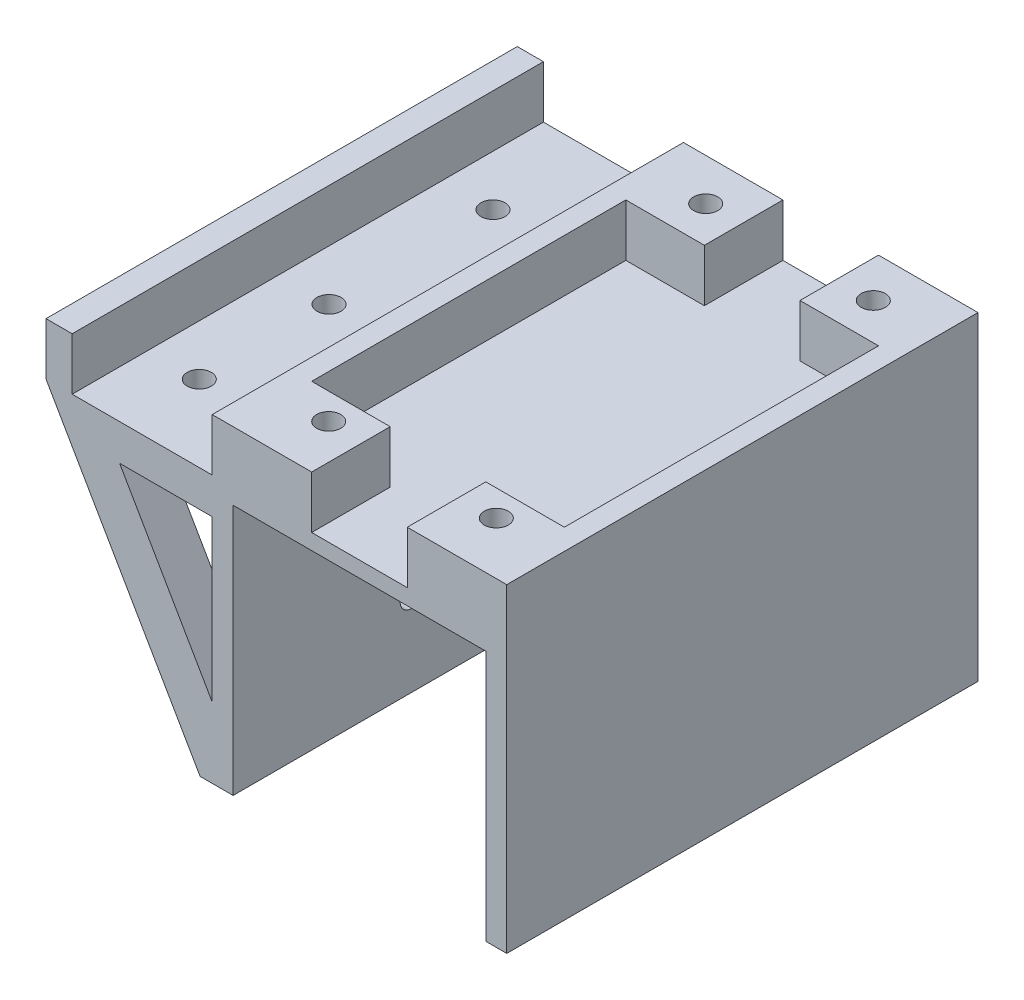
SolidWorks part; units mm, degrees
ref_plane "Front" through (0, 0, 0) normal (0, 0, 1) x (1, 0, 0)
ref_plane "Top" through (0, 0, 0) normal (0, 1, 0) x (1, 0, 0)
ref_plane "Right" through (0, 0, 0) normal (1, 0, 0) x (0, 0, -1)
sketch "Sketch1" plane through (0, 0, 0) normal (0, 0, 1) x (1, 0, 0)
  line L0 (0, 0) -> (0, 70)
  line L1 (0, 70) -> (56.254, 70)
  line L2 (56.254, 70) -> (56.254, 0)
  line L3 (56.254, 0) -> (52.254, 0)
  line L4 (52.254, 0) -> (52.254, 65)
  line L5 (52.254, 65) -> (4, 65)
  line L6 (4, 65) -> (4, 0)
  line L7 (4, 0) -> (0, 0)
  line L9 (4, 55) -> (52.254, 55)
  line L10 (4, 55) -> (4, 52)
  line L11 (4, 52) -> (52.254, 52)
  line L12 (52.254, 55) -> (52.254, 52)
  dimension "D1" = 48.254
  dimension "D2" = 4
  dimension "D3" = 4
  dimension "D4" = 5
  dimension "D5" = 70
  dimension "D6" = 3
  dimension "D7" = 10
extrude "Boss-Extrude1" add sketch "Sketch1" along normal blind 70 contours L7 L6 L5 L4 L3 L2 L1 L0 | L9 L12 L11 L10 region at (0.898, 35, 0)
sketch "Sketch3" plane through (0, 0, 70) normal (0, 0, 1) x (1, 0, 0)
  line L0 (0, 70) -> (-40.3946, 70)
  line L1 (-40.3946, 70) -> (0, 0.0344)
  line L2 (0, 0) -> (0, 70) construction
  line L3 (0, 0.0344) -> (0, 70)
  line L4 (0, 70) -> (0, 62.5)
  line L5 (0, 62.5) -> (-26, 62.5)
  line L6 (-26, 62.5) -> (0, 17.4667)
  line L7 (0, 17.4667) -> (0, 0.0344)
  line M11 (0, 70) -> (0, 0)
  dimension "D1" = 60
  dimension "D2" = 180
  dimension "D3" = 7.5
  dimension "D4" = 26
extrude "Boss-Extrude3" add sketch "Sketch3" against normal blind 8 contours L6 L5 L0 L1 M11 region at (-16.8587, 46.1047, 70)
sketch "Sketch4" plane through (0, 0, 0) normal (0, 0, -1) x (-1, 0, 0)
  line L0 (0, 70) -> (40.3946, 70)
  line L1 (40.3946, 70) -> (0, 0)
  line L2 (0, 0) -> (0, 17.4667)
  line L3 (0, 17.4667) -> (26, 62.5)
  line L4 (26, 62.5) -> (0, 62.5)
  line L5 (0, 62.5) -> (0, 70)
extrude "Boss-Extrude4" add sketch "Sketch4" against normal blind 8
ref_plane "Plane1" through (0, 0, 39) normal (0, 0, -1) x (-1, 0, 0)
sketch "Sketch5" plane through (0, 0, 39) normal (0, 0, -1) x (-1, 0, 0)
  line L0 (0, 62.5) -> (0, 70)
  line L1 (0, 70) -> (40.3946, 70)
  line L2 (40.3946, 70) -> (0, 0)
  line L3 (0, 0) -> (0, 17.4667)
  line L4 (0, 17.4667) -> (26, 62.5)
  line L5 (26, 62.5) -> (0, 62.5)
extrude "Boss-Extrude5" add sketch "Sketch5" along normal blind 8
sketch "Sketch6" plane through (0, 0, 0) normal (0, 0, -1) x (-1, 0, 0)
  line L5 (0, 62.5) -> (36.0666, 62.5)
  line L6 (0, 0) -> (40.3946, 70) construction
  line L7 (36.0666, 62.5) -> (40.3946, 70)
  line L8 (40.3946, 70) -> (0, 70)
  line L9 (40.3946, 70) -> (-56.254, 70) construction
  line L10 (0, 70) -> (0, 62.5)
  line L11 (-4, 0) -> (0, 0)
  line L12 (0, 0) -> (7.5019, 13)
  line L13 (7.5019, 13) -> (-4, 13)
  line L14 (-4, 52) -> (-4, 0) construction
  line L15 (-4, 13) -> (-4, 0)
  dimension "D1" = 13
extrude "Boss-Extrude6" add sketch "Sketch6" against normal blind 70
sketch "Sketch7" plane through (0, 0, 70) normal (0, 0, 1) x (1, 0, 0)
  line L0 (0, 17.4667) -> (0, 62.5) construction
  line L1 (-40.3946, 70) -> (0, 70)
  line L2 (-40.3946, 70) -> (-40.3946, 53)
  line L3 (-40.3946, 53) -> (0, 53)
  line L4 (0, 70) -> (0, 53)
  dimension "D1" = 17
extrude "Cut-Extrude3" cut sketch "Sketch7" against normal blind 70
sketch "Sketch8" plane through (0, 0, 0) normal (0, 0, -1) x (-1, 0, 0)
  line L1 (-4, 55) -> (-4, 52)
  line L2 (-4, 52) -> (-52.254, 52) construction
  line L3 (-4, 52) -> (30.0074, 52)
  line L4 (0, 0) -> (30.5845, 53) construction
  line L6 (30.0074, 52) -> (31.7386, 55)
  line L7 (31.7386, 55) -> (-4, 55)
  dimension "D1" = 180
extrude "Boss-Extrude7" add sketch "Sketch8" against normal blind 70
sketch "Sketch11" plane through (0, 0, 70) normal (0, 0, 1) x (1, 0, 0)
  line L0 (-31.7386, 55) -> (0, 0)
  line L3 (-31.7386, 55) -> (0, 55) construction
  line L4 (-27.289, 55) -> (-31.7386, 55)
  line L5 (-27.289, 55) -> (-3.0537, 13)
  line L6 (-3.0537, 13) -> (0, 0)
extrude "Boss-Extrude10" add sketch "Sketch11" against normal blind 8
sketch "Sketch12" plane through (0, 0, 70) normal (0, 0, 1) x (1, 0, 0)
  line L0 (-31.7386, 55) -> (-27.7598, 48.1051)
  line L1 (0, 0) -> (-31.7386, 55) construction
  line L2 (-27.7598, 48.1051) -> (0, 48.1051)
  line L3 (0, 17.4667) -> (0, 52) construction
  line L4 (0, 48.1051) -> (0, 55)
  line L5 (0, 55) -> (-31.7386, 55)
extrude "Boss-Extrude11" add sketch "Sketch12" against normal blind 70
sketch "Sketch13" plane through (0, 0, 0) normal (0, -1, 0) x (1, 0, 0)
  line L1 (67.4394, -10.6205) -> (-15.562, -10.6205)
  line L2 (67.4394, -10.6205) -> (67.4394, 77.2481)
  line L3 (67.4394, 77.2481) -> (-15.562, 77.2481)
  line L4 (-15.562, -10.6205) -> (-15.562, 77.2481)
extrude "Cut-Extrude4" cut sketch "Sketch13" against normal blind 4
sketch "Sketch14" plane through (0, 0, 70) normal (0, 0, 1) x (1, 0, 0)
  line L0 (-2.3083, 4) -> (-31.7386, 55)
  line L1 (-31.7386, 55) -> (0, 55)
  line L2 (0, 55) -> (0, 70)
  line L3 (0, 70) -> (56.254, 70)
  line L4 (56.254, 70) -> (56.254, 4)
  line L5 (56.254, 4) -> (52.254, 4)
  line L6 (52.254, 4) -> (52.254, 52)
  line L7 (52.254, 52) -> (4, 52)
  line L8 (4, 52) -> (4, 4)
  line L9 (4, 4) -> (-2.3083, 4)
  line L14 (-17.6891, 48.1051) -> (0, 48.1051)
  line L15 (52.254, 55) -> (4, 55)
  line L16 (52.254, 55) -> (52.254, 65)
  line L17 (52.254, 65) -> (4, 65)
  line L18 (4, 55) -> (4, 65)
  line L19 (-17.6891, 48.1051) -> (0, 48.1051) construction
  line L20 (0, 48.1051) -> (0, 17.4667)
  line L21 (0, 17.4667) -> (-17.6891, 48.1051)
extrude "Boss-Extrude12" add sketch "Sketch14" along normal blind 20
sketch "Sketch15" plane through (0, 0, 90) normal (0, 0, 1) x (1, 0, 0)
  line L0 (56.254, 4) -> (56.254, 70) construction
  line L1 (56.254, 65) -> (37.264, 65)
  line L2 (56.254, 65) -> (56.254, 55)
  line L3 (56.254, 55) -> (37.264, 55)
  line L4 (37.264, 65) -> (37.264, 55)
  line L5 (4, 55) -> (52.254, 55) construction
  dimension "D1" = 18.99
sketch "Sketch16" plane through (0, 0, 90) normal (0, 0, 1) x (1, 0, 0)
  line L1 (0, 70) -> (56.254, 70)
  line L2 (0, 70) -> (0, 65)
  line L3 (0, 65) -> (56.254, 65)
  line L4 (56.254, 70) -> (56.254, 65)
extrude "Cut-Extrude5" cut sketch "Sketch16" against normal blind 100
sketch "Sketch17" plane through (0, 65, 0) normal (0, 1, 0) x (1, 0, 0)
  line L1 (52.254, 0) -> (37.254, 0)
  line L2 (52.254, 0) -> (52.254, -15)
  line L3 (52.254, -15) -> (37.254, -15)
  line L4 (37.254, 0) -> (37.254, -15)
  line L5 (52.254, -90) -> (37.254, -90)
  line L6 (52.254, -90) -> (52.254, -75)
  line L7 (52.254, -75) -> (37.254, -75)
  line L8 (37.254, -90) -> (37.254, -75)
  dimension "D1" = 15
  dimension "D2" = 15
  dimension "D3" = 15
  dimension "D4" = 15
extrude "Boss-Extrude14" add sketch "Sketch17" against normal blind 13
sketch "Sketch21" plane through (0, 52, 0) normal (0, -1, 0) x (-1, 0, 0)
  circle A0 centre (-44.254, -80) radius 2.3
  circle A1 centre (-44.254, -8) radius 2.3
sketch "Sketch22" plane through (0, 52, 0) normal (0, -1, 0) x (1, 0, 0)
  line L1 (48.0965, 6.0036) -> (47.9041, 10.3295)
  line L2 (47.9041, 10.3295) -> (44.0617, 12.3259)
  line L3 (44.0617, 12.3259) -> (40.4115, 9.9964)
  line L4 (40.4115, 9.9964) -> (40.6039, 5.6705)
  line L5 (40.6039, 5.6705) -> (44.4463, 3.6741)
  line L6 (44.4463, 3.6741) -> (48.0965, 6.0036)
  line L7 (45.2007, 75.7746) -> (48.3866, 78.7072)
  line L8 (48.3866, 78.7072) -> (47.4399, 82.9325)
  line L9 (47.4399, 82.9325) -> (43.3073, 84.2254)
  line L10 (43.3073, 84.2254) -> (40.1214, 81.2928)
  line L11 (40.1214, 81.2928) -> (41.0681, 77.0675)
  line L12 (41.0681, 77.0675) -> (45.2007, 75.7746)
  circle A0 centre (44.254, 8) radius 3.75 construction
  circle A1 centre (44.254, 80) radius 3.75 construction
  point P10 (42.2366, 11.1611)
  dimension "D1" = 7.5
  dimension "D2" = 7.5
extrude "Cut-Extrude8" cut sketch "Sketch22" against normal blind 5
extrude "Cut-Extrude9" cut sketch "Sketch21" against normal blind 15
sketch "Sketch23" plane through (0, 0, 0) normal (-0.8661, -0.4998, 0) x (0, 0, 1)
  line L0 (90, 63.5007) -> (90, 4.6182) construction
  line L1 (70, 55.5401) -> (82, 55.5401)
  line L2 (70, 55.5401) -> (70, 15.0093)
  line L3 (70, 15.0093) -> (82, 15.0093)
  line L4 (82, 55.5401) -> (82, 15.0093)
  line L5 (62, 55.5401) -> (62, 15.0093) construction
  dimension "D1" = 8
  dimension "D2" = 8
extrude "Cut-Extrude10" cut sketch "Sketch23" against normal blind 9
sketch "Sketch25" plane through (0, 48.1051, 0) normal (0, -1, 0) x (-1, 0, 0)
  circle A0 centre (17.0755, -19.3006) radius 2.3
  circle A1 centre (17.0755, -50.6137) radius 2.3
extrude "Cut-Extrude11" cut sketch "Sketch25" against normal blind 20
sketch "Sketch26" plane through (0, 48.1051, 0) normal (0, -1, 0) x (1, 0, 0)
  circle A0 centre (-17.0755, 75.3913) radius 2.3
extrude "Cut-Extrude12" cut sketch "Sketch26" against normal blind 20
sketch "Sketch27" plane through (0, 0, 90) normal (0, 0, 1) x (1, 0, 0)
  line L0 (-23.3104, 48.1051) -> (-27.7598, 48.1051)
  line L1 (-31.7386, 55) -> (-2.3083, 4) construction
  line L2 (-27.7598, 48.1051) -> (-31.7386, 55)
  line L3 (-31.7386, 55) -> (-23.3104, 55)
  line L4 (0, 55) -> (-31.7386, 55) construction
  line L5 (-23.3104, 55) -> (-23.3104, 48.1051)
extrude "Boss-Extrude16" add sketch "Sketch27" against normal blind 20
sketch "Sketch28" plane through (0, 55, 0) normal (0, 1, 0) x (1, 0, 0)
  line L0 (4, -90) -> (37.254, -90) construction
  line L1 (4, 0) -> (19, 0)
  line L2 (4, 0) -> (4, -15)
  line L3 (4, -15) -> (19, -15)
  line L4 (19, 0) -> (19, -15)
  line L5 (4, -90) -> (19, -90)
  line L6 (4, -90) -> (4, -75)
  line L7 (4, -75) -> (19, -75)
  line L8 (19, -90) -> (19, -75)
  line L9 (4, 0) -> (4, -90) construction
  dimension "D1" = 15
  dimension "D2" = 15
  dimension "D3" = 15
  dimension "D4" = 15
extrude "Boss-Extrude17" add sketch "Sketch28" along normal blind 10
sketch "Sketch29" plane through (0, 52, 0) normal (0, -1, 0) x (-1, 0, 0)
  circle A0 centre (-12.254, -8) radius 2.3
  circle A1 centre (-12.254, -80) radius 2.3
extrude "Cut-Extrude13" cut sketch "Sketch29" against normal blind 20
sketch "Sketch30" plane through (0, 48.1051, 0) normal (0, -1, 0) x (1, 0, 0)
  line L1 (-27.7598, 70) -> (-17.3688, 70)
  line L2 (-27.7598, 70) -> (-27.7598, 82)
  line L3 (-27.7598, 82) -> (-17.3688, 82)
  line L4 (-17.3688, 70) -> (-17.3688, 82)
extrude "Boss-Extrude18" add sketch "Sketch30" against normal blind 5
sketch "Sketch31" plane through (0, 48.1051, 0) normal (0, -1, 0) x (1, 0, 0)
  circle A0 centre (-17.0755, 75.3913) radius 2.3
extrude "Cut-Extrude14" cut sketch "Sketch31" against normal blind 45
sketch "Sketch36" plane through (0, 55, 0) normal (0, 1, 0) x (1, 0, 0)
  line L0 (0, -90) -> (-31.7386, -90) construction
  line L1 (-31.7386, 0) -> (-31.1386, 0)
  line L2 (-31.7386, 0) -> (-31.7386, -90)
  line L3 (-31.7386, -90) -> (-31.1386, -90)
  line L4 (-31.1386, 0) -> (-31.1386, -90)
  line L5 (-27.5386, 0) -> (-27.5386, -90)
  line L6 (-27.5386, 0) -> (-26.9386, 0)
  line L7 (-26.9386, 0) -> (-26.9386, -90)
  line L8 (-27.5386, -90) -> (-26.9386, -90)
  line L9 (-23.3386, 0) -> (-23.3386, -90)
  line L10 (-23.3386, 0) -> (-22.7386, 0)
  line L11 (-22.7386, 0) -> (-22.7386, -90)
  line L12 (-23.3386, -90) -> (-22.7386, -90)
  line L13 (-19.1386, 0) -> (-19.1386, -90)
  line L14 (-19.1386, 0) -> (-18.5386, 0)
  line L15 (-18.5386, 0) -> (-18.5386, -90)
  line L16 (-19.1386, -90) -> (-18.5386, -90)
  line L17 (-14.9386, 0) -> (-14.9386, -90)
  line L18 (-14.9386, 0) -> (-14.3386, 0)
  line L19 (-14.3386, 0) -> (-14.3386, -90)
  line L20 (-14.9386, -90) -> (-14.3386, -90)
  line L21 (-10.7386, 0) -> (-10.7386, -90)
  line L22 (-10.7386, 0) -> (-10.1386, 0)
  line L23 (-10.1386, 0) -> (-10.1386, -90)
  line L24 (-10.7386, -90) -> (-10.1386, -90)
  line L25 (-6.5386, 0) -> (-6.5386, -90)
  line L26 (-6.5386, 0) -> (-5.9386, 0)
  line L27 (-5.9386, 0) -> (-5.9386, -90)
  line L28 (-6.5386, -90) -> (-5.9386, -90)
  line L29 (-2.3386, 0) -> (-2.3386, -90)
  line L30 (-2.3386, 0) -> (-1.7386, 0)
  line L31 (-1.7386, 0) -> (-1.7386, -90)
  line L32 (-2.3386, -90) -> (-1.7386, -90)
  line L33 (-31.7386, 0) -> (-27.5386, 0) construction
  dimension "D1" = 0.6
  dimension "D3" = 4.2
  dimension "D2" = 8
sketch "Sketch37" plane through (0, 55, 0) normal (0, 1, 0) x (1, 0, 0)
  line L0 (19, 0) -> (37.254, 0) construction
  line L13 (4, -6) -> (4, -6.5)
  line L14 (4, -15) -> (4, -75) construction
  line L15 (4, -2) -> (53, -2)
  line L16 (4, -2) -> (4, -2.5)
  line L17 (4, -2.5) -> (53, -2.5)
  line L18 (53, -2) -> (53, -2.5)
  line L19 (4, -6) -> (53, -6)
  line L20 (53, -6) -> (53, -6.5)
  line L21 (4, -6.5) -> (53, -6.5)
  line L22 (4, -10) -> (4, -10.5)
  line L23 (4, -10) -> (53, -10)
  line L24 (53, -10) -> (53, -10.5)
  line L25 (4, -10.5) -> (53, -10.5)
  line L26 (4, -14) -> (4, -14.5)
  line L27 (4, -14) -> (53, -14)
  line L28 (53, -14) -> (53, -14.5)
  line L29 (4, -14.5) -> (53, -14.5)
  line L30 (4, -18) -> (4, -18.5)
  line L31 (4, -18) -> (53, -18)
  line L32 (53, -18) -> (53, -18.5)
  line L33 (4, -18.5) -> (53, -18.5)
  line L34 (4, -22) -> (4, -22.5)
  line L35 (4, -22) -> (53, -22)
  line L36 (53, -22) -> (53, -22.5)
  line L37 (4, -22.5) -> (53, -22.5)
  line L38 (4, -26) -> (4, -26.5)
  line L39 (4, -26) -> (53, -26)
  line L40 (53, -26) -> (53, -26.5)
  line L41 (4, -26.5) -> (53, -26.5)
  line L42 (4, -30) -> (4, -30.5)
  line L43 (4, -30) -> (53, -30)
  line L44 (53, -30) -> (53, -30.5)
  line L45 (4, -30.5) -> (53, -30.5)
  line L46 (4, -34) -> (4, -34.5)
  line L47 (4, -34) -> (53, -34)
  line L48 (53, -34) -> (53, -34.5)
  line L49 (4, -34.5) -> (53, -34.5)
  line L50 (4, -38) -> (4, -38.5)
  line L51 (4, -38) -> (53, -38)
  line L52 (53, -38) -> (53, -38.5)
  line L53 (4, -38.5) -> (53, -38.5)
  line L54 (4, -42) -> (4, -42.5)
  line L55 (4, -42) -> (53, -42)
  line L56 (53, -42) -> (53, -42.5)
  line L57 (4, -42.5) -> (53, -42.5)
  line L58 (4, -46) -> (4, -46.5)
  line L59 (4, -46) -> (53, -46)
  line L60 (53, -46) -> (53, -46.5)
  line L61 (4, -46.5) -> (53, -46.5)
  line L62 (4, -50) -> (4, -50.5)
  line L63 (4, -50) -> (53, -50)
  line L64 (53, -50) -> (53, -50.5)
  line L65 (4, -50.5) -> (53, -50.5)
  line L66 (4, -54) -> (4, -54.5)
  line L67 (4, -54) -> (53, -54)
  line L68 (53, -54) -> (53, -54.5)
  line L69 (4, -54.5) -> (53, -54.5)
  line L70 (4, -58) -> (4, -58.5)
  line L71 (4, -58) -> (53, -58)
  line L72 (53, -58) -> (53, -58.5)
  line L73 (4, -58.5) -> (53, -58.5)
  line L74 (4, -62) -> (4, -62.5)
  line L75 (4, -62) -> (53, -62)
  line L76 (53, -62) -> (53, -62.5)
  line L77 (4, -62.5) -> (53, -62.5)
  line L78 (4, -66) -> (4, -66.5)
  line L79 (4, -66) -> (53, -66)
  line L80 (53, -66) -> (53, -66.5)
  line L81 (4, -66.5) -> (53, -66.5)
  line L82 (4, -70) -> (4, -70.5)
  line L83 (4, -70) -> (53, -70)
  line L84 (53, -70) -> (53, -70.5)
  line L85 (4, -70.5) -> (53, -70.5)
  line L86 (4, -74) -> (4, -74.5)
  line L87 (4, -74) -> (53, -74)
  line L88 (53, -74) -> (53, -74.5)
  line L89 (4, -74.5) -> (53, -74.5)
  line L90 (4, -78) -> (4, -78.5)
  line L91 (4, -78) -> (53, -78)
  line L92 (53, -78) -> (53, -78.5)
  line L93 (4, -78.5) -> (53, -78.5)
  line L94 (4, -82) -> (4, -82.5)
  line L95 (4, -82) -> (53, -82)
  line L96 (53, -82) -> (53, -82.5)
  line L97 (4, -82.5) -> (53, -82.5)
  line L98 (4, -86) -> (4, -86.5)
  line L99 (4, -86) -> (53, -86)
  line L100 (53, -86) -> (53, -86.5)
  line L101 (4, -86.5) -> (53, -86.5)
  dimension "D1" = 49
  dimension "D2" = 0.5
  dimension "D3" = 2
  dimension "D4" = 22
sketch "Sketch40" plane through (0, 65, 0) normal (0, 1, 0) x (1, 0, 0)
  circle A0 centre (-17.0755, -19.3006) radius 2.2732
  circle A1 centre (-17.0755, -50.6137) radius 2.3827
  circle A2 centre (-17.0755, -75.3913) radius 2.3828
  circle A3 centre (12.254, -80) radius 2.5607
  circle A4 centre (44.254, -80) radius 2.2791
  circle A5 centre (44.254, -8) radius 2.3112
  circle A6 centre (12.254, -8) radius 2.3
sketch "Sketch41" plane through (0, 55, 0) normal (0, 1, 0) x (1, 0, 0)
  line L0 (-31.7386, 0) -> (0, 0) construction
  line L1 (-31.7386, -90) -> (-26.7386, -90)
  line L2 (-31.7386, -90) -> (-31.7386, 0)
  line L3 (-31.7386, 0) -> (-26.7386, 0)
  line L4 (-26.7386, -90) -> (-26.7386, 0)
  dimension "D1" = 5
extrude "Boss-Extrude19" add sketch "Sketch41" along normal blind 10
sketch "Sketch42" plane through (0, 52, 0) normal (0, -1, 0) x (1, 0, 0)
  line L1 (14.1516, 76.1078) -> (16.5735, 79.6973)
  line L2 (16.5735, 79.6973) -> (14.6759, 83.5895)
  line L3 (14.6759, 83.5895) -> (10.3564, 83.8922)
  line L4 (10.3564, 83.8922) -> (7.9345, 80.3027)
  line L5 (7.9345, 80.3027) -> (9.8321, 76.4105)
  line L6 (9.8321, 76.4105) -> (14.1516, 76.1078)
  line L7 (13.8189, 3.9626) -> (16.533, 7.3365)
  line L8 (16.533, 7.3365) -> (14.9681, 11.374)
  line L9 (14.9681, 11.374) -> (10.6891, 12.0374)
  line L10 (10.6891, 12.0374) -> (7.975, 8.6635)
  line L11 (7.975, 8.6635) -> (9.5399, 4.626)
  line L12 (9.5399, 4.626) -> (13.8189, 3.9626)
  circle A0 centre (12.254, 80) radius 3.75 construction
  circle A1 centre (12.254, 8) radius 3.75 construction
  dimension "D1" = 7.5
  dimension "D2" = 7.5
extrude "Cut-Extrude15" cut sketch "Sketch42" against normal blind 5
sketch "Sketch43" plane through (4, 0, 0) normal (1, 0, 0) x (0, 0, -1)
  circle A4 centre (-56, 36) radius 2.1
sketch "Sketch44" plane through (4, 0, 0) normal (1, 0, 0) x (0, 0, -1)
  circle A1 centre (-56, 20) radius 2.1
  circle A3 centre (-16, 20) radius 2.1
extrude "Cut-Extrude16" cut sketch "Sketch43" against normal blind 5
extrude "Cut-Extrude17" cut sketch "Sketch44" against normal blind 5
sketch "Sketch45" plane through (0, 0, 0) normal (-1, 0, 0) x (0, 0, 1)
  circle A0 centre (16, 36) radius 2.1
  circle A1 centre (16, 20) radius 2.1 construction
  circle A2 centre (56, 36) radius 2.1 construction
  dimension "D1" = 16
  dimension "D2" = 40
extrude "Cut-Extrude18" cut sketch "Sketch45" against normal blind 5
